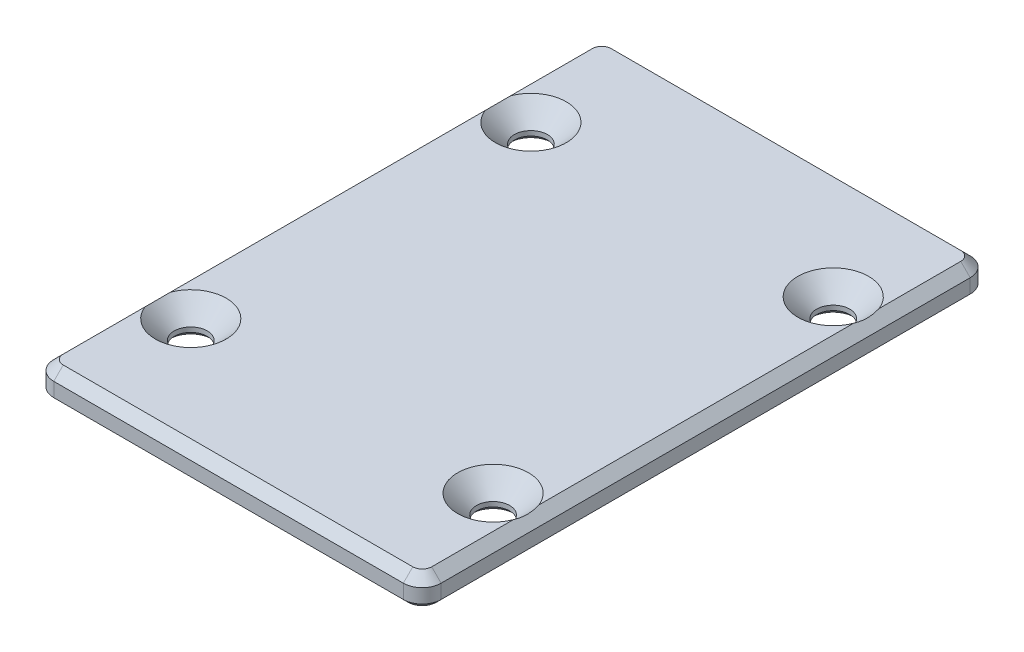
SolidWorks part; units mm, degrees
ref_plane "Спереди" through (0, 0, 0) normal (0, 0, 1) x (1, 0, 0)
ref_plane "Сверху" through (0, 0, 0) normal (0, 1, 0) x (1, 0, 0)
ref_plane "Справа" through (0, 0, 0) normal (1, 0, 0) x (0, 0, -1)
sketch "Эскиз1" plane through (0, 0, 0) normal (0, 1, 0) x (1, 0, 0)
  line L1 (-20.5, -30) -> (20.5, -30)
  line L2 (-20.5, -30) -> (-20.5, 30)
  line L3 (-20.5, 30) -> (20.5, 30)
  line L4 (20.5, -30) -> (20.5, 30)
  line L5 (0, 30) -> (0, -30) construction
  line L6 (-20.5, 0) -> (20.5, 0) construction
  point P0 (0, 0)
  dimension "D1" = 60
  dimension "D2" = 41
extrude "Бобышка-Вытянуть1" add sketch "Эскиз1" along normal blind 3
sketch "Эскиз2" plane through (0, 3, 0) normal (0, 1, 0) x (1, 0, 0)
  line L0 (0, 32.2776) -> (0, 0) construction
  line L1 (0, 0) -> (26.8846, 0) construction
  line L2 (20.5, -30) -> (20.5, 30) construction
  circle A0 centre (16, 18) radius 1.75
  circle A1 centre (16, -18) radius 1.75
  circle A2 centre (-16, -18) radius 1.75
  circle A3 centre (-16, 18) radius 1.75
  dimension "D1" = 18
  dimension "D2" = 4.5
  dimension "D3" = 3.5
extrude "Вырез-Вытянуть1" cut sketch "Эскиз2" against normal blind 3
fillet "Скругление1" radius 2 4 edges at (20.5, 1.5, -30) (-20.5, 1.5, -30) (-20.5, 1.5, 30) (20.5, 1.5, 30)
sketch "Эскиз3" plane through (0, 0, 0) normal (0, -1, 0) x (1, 0, 0)
  line L0 (0, 32.2375) -> (0, 0) construction
  line L1 (0, 0) -> (33.8614, 0) construction
  line L2 (-18.5, 30) -> (18.5, 30) construction
  line L3 (-12.5, 22) -> (12.5, 22)
  line L4 (-12.5, 22) -> (-12.5, 30)
  line L5 (-12.5, 30) -> (12.5, 30)
  line L6 (12.5, 22) -> (12.5, 30)
  line L7 (0, 30) -> (0, 22) construction
  line L8 (-12.5, 26) -> (12.5, 26) construction
  point P3 (0, 26)
  dimension "D1" = 25
  dimension "D2" = 8
extrude "Бобышка-Вытянуть2" [suppressed] add sketch "Эскиз3" along normal blind 5
fillet "Скругление2" [suppressed] radius 1
chamfer "Фаска2" distance 1 angle 45 8 edges at (-20.5, 3, 0) (19.9142, 3, -29.4142) (-19.9142, 3, -29.4142) (0, 3, -30) (-19.9142, 3, 29.4142) (0, 3, 30) (19.9142, 3, 29.4142) (20.5, 3, 0)
chamfer "Фаска1" distance 2 angle 45 4 edges at (-16, 3, 19.75) (16, 3, 16.25) (-16, 3, -19.75) (16, 3, -16.25)
sketch "Эскиз4" plane through (0, 3, 0) normal (0, 1, 0) x (1, 0, 0)
  line L0 (23.4186, 22.1575) -> (1.1874, 22.1575)
  line L1 (23.4186, 10.6017) -> (2.0235, 10.6017)
  line L2 (23.4186, 28.2171) -> (23.4186, 3.4703) construction
  line L3 (23.4186, 22.1575) -> (23.4186, 10.6017)
  arc A0 (1.1874, 22.1575) -> (2.0235, 10.6017) centre (-0.0813, 16.2575) ccw
extrude "Вырез-Вытянуть3" [suppressed] cut sketch "Эскиз4" against normal blind 10
chamfer "Фаска3" distance 0.5 angle 45 12 edges at (-19.9142, 0, -29.4142) (-20.5, 0, 0) (-19.9142, 0, 29.4142) (0, 0, 30) (19.9142, 0, 29.4142) (20.5, 0, 0) (19.9142, 0, -29.4142) (0, 0, -30) (16, 0, -16.25) (16, 0, 16.25) (-16, 0, 19.75) (-16, 0, -19.75)
